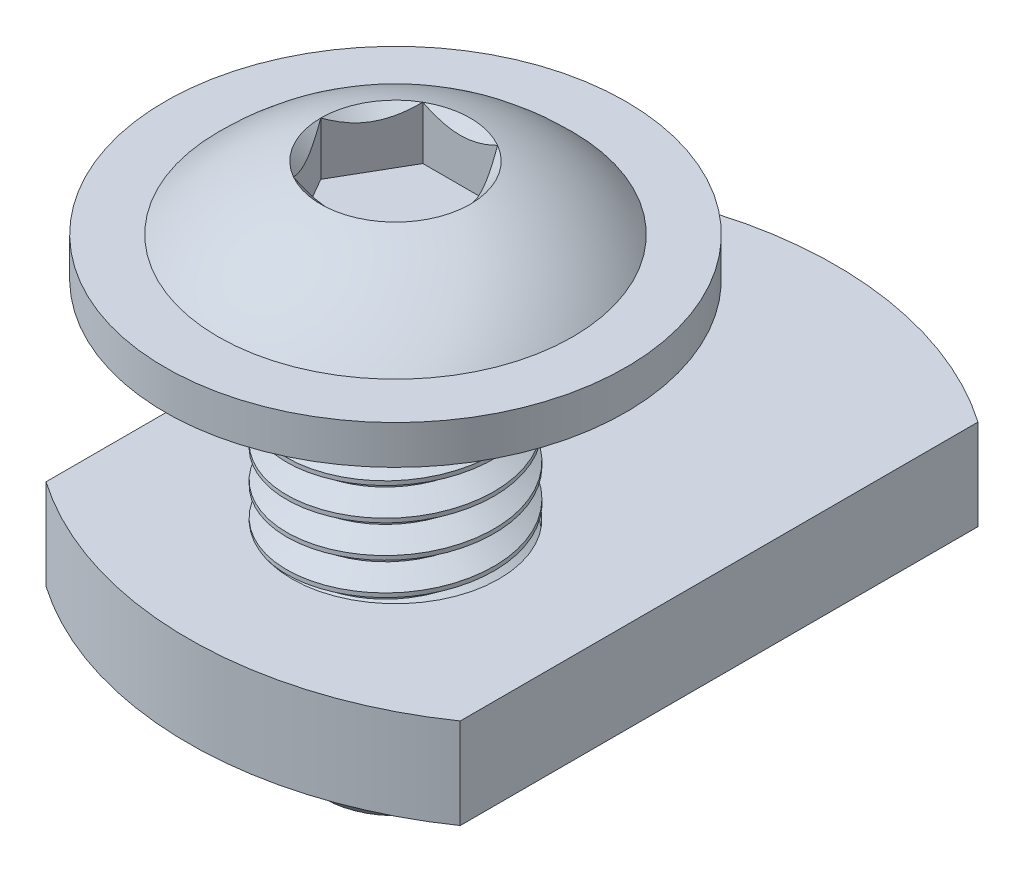
SolidWorks part; units mm, degrees
ref_plane "Front Plane" through (0, 0, 0) normal (0, 0, 1) x (1, 0, 0)
ref_plane "Top Plane" through (0, 0, 0) normal (0, 1, 0) x (1, 0, 0)
ref_plane "Right Plane" through (0, 0, 0) normal (1, 0, 0) x (0, 0, -1)
sketch "Sketch1" plane through (0, 0, 0) normal (0, 0, 1) x (1, 0, 0)
  line L0 (0, 0) -> (0, 20.4) construction
  line L1 (0, 0) -> (-4, 0)
  line L2 (-4, 0) -> (-4, 16)
  line L3 (-4, 16) -> (-6.85, 16)
  line L4 (-6.85, 16) -> (-6.85, 17.5)
  line L6 (0, 0) -> (0, 20.4)
  arc A0 (-6.85, 17.5) -> (0, 20.4) centre (0, 10.8599) cw
  dimension "screw od" = 8
  dimension "head od" = 13.7
  dimension "D4" = 1.5
  dimension "head height" = 4.4
  dimension "screw length" = 16
sketch "Sketch2" plane through (0, 0, 0) normal (0, 0, 1) x (1, 0, 0)
  line L0 (0, 0) -> (0, 20.4) construction
  line L1 (-4, 16) -> (-6.85, 16) construction
  line L2 (0, 0) -> (-4, 0) construction
  line L3 (-4, 0) -> (-4, 16) construction
  line L4 (0, 0) -> (0, 16)
  line L5 (0, 16) -> (-4, 16)
  line L6 (0, 0) -> (-4, 0)
  line L7 (-4, 0) -> (-4, 16)
revolve "Revolve2" add sketch "Sketch2" angle 360 about L0
sketch "Sketch3" plane through (0, 16, 0) normal (0, 1, 0) x (1, 0, 0)
  circle A1 centre (0, 0) radius 4
  circle A2 centre (0, 0) radius 4
  dimension "D1" = 0
curve "Helix/Spiral1" pitch 1.25 height 16.1875 turns 12.95 parameters "pitch"=1.25
chamfer "Chamfer1" distance 1.25 angle 45 1 edges at (0, 0, -4)
sketch "Sketch4" plane through (0, 0, 0) normal (0, 0, 1) x (1, 0, 0)
  line L0 (4, 17.0938) -> (4, 16)
  line L1 (4, 16) -> (3.1881, 16.4688)
  line L2 (3.1881, 16.4688) -> (3.1881, 16.625)
  line L3 (3.1881, 16.625) -> (4, 17.0938)
  line L4 (3.1881, 16.5469) -> (4, 16.5469) construction
  line L5 (3.5941, 16.2344) -> (3.5941, 16.8594) construction
  line L7 (4, 16) -> (-4, 16) construction
  dimension "D1" = 60
  dimension "D2" = 0.1562
  dimension "D3" = 0.625
sweep "Cut-Sweep1" cut profiles "Sketch4" path "Helix/Spiral1"
sketch "Sketch5" plane through (0, 0, 0) normal (0, 0, 1) x (1, 0, 0)
  line L0 (0, 0) -> (0, 20.4) construction
  line L1 (-4, 16) -> (-6.85, 16) construction
  line L3 (-6.85, 16) -> (-6.85, 17.5) construction
  line L4 (0, 16) -> (0, 20.4)
  line L5 (0, 16) -> (-6.85, 16)
  line L7 (-6.85, 16) -> (-6.85, 17.5)
  arc A0 (0, 20.4) -> (-6.85, 17.5) centre (0, 10.8599) ccw construction
  arc A1 (0, 20.4) -> (-6.85, 17.5) centre (0, 10.8599) ccw
revolve "Revolve3" add sketch "Sketch5" angle 360 about L0
sketch "Sketch20" plane through (0, 16, 0) normal (0, -1, 0) x (1, 0, 0)
  circle A0 centre (0, 0) radius 8.9
  dimension "D1" = 17.8
extrude "Boss-Extrude1" add sketch "Sketch20" against normal blind 1.5
ref_plane "Plane1" through (0, 20.4, 0) normal (0, 1, 0) x (-1, 0, 0)
sketch "Sketch6" plane through (0, 20.4, 0) normal (0, 1, 0) x (-1, 0, 0)
  line L1 (1.4434, 2.5) -> (-1.4434, 2.5)
  line L2 (-1.4434, 2.5) -> (-2.8868, 0)
  line L3 (-2.8868, 0) -> (-1.4434, -2.5)
  line L4 (-1.4434, -2.5) -> (1.4434, -2.5)
  line L5 (1.4434, -2.5) -> (2.8868, 0)
  line L6 (2.8868, 0) -> (1.4434, 2.5)
  circle A0 centre (0, 0) radius 2.5 construction
  dimension "hex" = 5
extrude "Cut-Extrude1" cut sketch "Sketch6" against normal blind 2.5
ref_plane "Plane2" through (0, 19.9528, 0) normal (0, 1, 0) x (-1, 0, 0)
sketch "Sketch7" plane through (0, 19.9528, 0) normal (0, 1, 0) x (-1, 0, 0)
  circle A0 centre (0, 0) radius 2.8868
extrude "Cut-Extrude2" cut sketch "Sketch7" against normal up to surface (2.0528 mm away) draft 45 and the other way through all
ref_plane "Plane3" through (0, 5.475, 0) normal (0, -1, 0) x (1, 0, 0)
sketch "Sketch8" [suppressed] plane through (0, 2.475, 0) normal (0, -1, 0) x (1, 0, 0)
  line L0 (-4, -2.5) -> (4, -2.5) construction
  line L1 (0, -2.5) -> (0, 0) construction
  line L2 (-4, 3.5) -> (-4, -8.5)
  line L4 (4, 3.5) -> (4, -8.5)
  circle A0 centre (0, 0) radius 2.5
  arc A1 (-4, 3.5) -> (4, 3.5) centre (0, -1.0833) cw
  arc A2 (-4, -8.5) -> (4, -8.5) centre (0, -3.9167) ccw
  dimension "D1" = 26.4706
  dimension "D4" = 3.9167
  dimension "D3" = 33.0883
  dimension "D2" = 12.7
extrude "Extrude1" [suppressed] add sketch "Sketch8" along normal mid plane 3 separate body
sketch "Sketch9" [suppressed] plane through (0, 0.975, 0) normal (0, -1, 0) x (1, 0, 0)
  line L2 (4, -8.5) -> (4, 3.5)
  line L3 (-4, 3.5) -> (-4, -8.5)
  line L4 (4, -8.5) -> (4, 3.5)
  line L5 (-4, 3.5) -> (-4, -8.5)
  circle A0 centre (0, 0) radius 3
  arc A2 (-4, -8.5) -> (4, -8.5) centre (0, -3.9167) ccw
  arc A3 (4, 3.5) -> (-4, 3.5) centre (0, -1.0833) ccw
  arc A4 (-4, -8.5) -> (4, -8.5) centre (0, -3.9167) ccw
  arc A5 (4, 3.5) -> (-4, 3.5) centre (0, -1.0833) ccw
  dimension "D2" = 6
  dimension "D1" = 0
extrude "Cut-Extrude3" [suppressed] cut sketch "Sketch9" against normal offset from surface (1 mm away) 2
sketch "Sketch10" plane through (0, 5.475, 0) normal (0, -1, 0) x (1, 0, 0)
  line L0 (-8, -14.5) -> (-8, 5.5)
  line L1 (8, 5.5) -> (8, -14.5)
  line L2 (-18.9844, 8) -> (0, 8) construction
  circle A0 centre (0, 0) radius 4
  arc A1 (8, 5.5) -> (-8, 5.5) centre (0, -6.05) ccw
  arc A2 (-8, -14.5) -> (8, -14.5) centre (0, -2.95) ccw
  dimension "D2" = 8
  dimension "D3" = 16
  dimension "D4" = 2.5
  dimension "D5" = 8
  dimension "D1" = 25
extrude "Extrude2" add sketch "Sketch10" along normal mid plane 5 separate body
sketch "Sketch11" plane through (0, 2.975, 0) normal (0, -1, 0) x (1, 0, 0)
  line L2 (8, -14.5) -> (8, 5.5)
  line L3 (-8, 5.5) -> (-8, -14.5)
  line L4 (8, -14.5) -> (8, 5.5)
  line L5 (-8, 5.5) -> (-8, -14.5)
  circle A0 centre (0, 0) radius 2.75 construction
  circle A3 centre (0, 0) radius 4.5
  arc A5 (-8, -14.5) -> (8, -14.5) centre (0, -2.95) ccw
  arc A6 (8, 5.5) -> (-8, 5.5) centre (0, -6.05) ccw
  arc A7 (-8, -14.5) -> (8, -14.5) centre (0, -2.95) ccw
  arc A8 (8, 5.5) -> (-8, 5.5) centre (0, -6.05) ccw
  dimension "D1" = 9
  dimension "D2" = 0
extrude "Cut-Extrude4" cut sketch "Sketch11" against normal offset from surface (1.5 mm away) 3.5 up to face at (0, 7.975, -4.5)
sketch "Sketch12" [suppressed] plane through (0, 0, 0) normal (0, 0, 1) x (1, 0, 0)
  line L0 (-6.8072, 17.78) -> (-5.4458, 17.78) construction
  line L1 (-6.8072, 17.78) -> (-5.4458, 17.78)
  line L2 (9.2481, 20.0393) -> (-9.2481, 20.0393) construction
  line L3 (0, 0) -> (0, 53.1234) construction
  line L4 (-3.9688, 15.875) -> (-6.8072, 15.875) construction
  line L5 (-9.398, 15.875) -> (-3.9688, 15.875)
  line L6 (-9.398, 15.875) -> (-9.398, 14.605)
  line L7 (-9.398, 14.605) -> (-3.9688, 14.605)
  line L8 (-3.9688, 15.875) -> (-3.9688, 14.605)
  arc A0 (0, 20.6375) -> (-5.4458, 17.78) centre (0, 14.0195) ccw construction
  arc A1 (-2.7496, 20.0393) -> (-5.4458, 17.78) centre (0, 14.0195) ccw
  arc A2 (-6.8072, 17.78) -> (-2.7496, 20.0393) centre (0, 10.3277) cw
  dimension "D1" = 9.398
  dimension "D2" = 1.27
revolve "Revolve4" [suppressed] add sketch "Sketch12" angle 360 about L0
sketch "Sketch13" [suppressed] plane through (0, 6.35, 0) normal (0, -1, 0) x (1, 0, 0)
  line L0 (-7.9375, 4.7562) -> (-7.9375, -17.4688)
  line L1 (7.9375, 4.7562) -> (7.9375, -17.4688)
  circle A0 centre (0, 0) radius 3.9688
  arc A1 (-7.9375, 4.7562) -> (7.9375, 4.7562) centre (0, -3.5782) cw
  arc A2 (-7.9375, -17.4688) -> (7.9375, -17.4688) centre (0, -9.1345) ccw
  dimension "D2" = 28.575
  dimension "D3" = 3.9624
  dimension "D4" = 7.9375
  dimension "D1" = 15.875
  dimension "D5" = 3.175
extrude "Extrude4" [suppressed] add sketch "Sketch13" along normal mid plane 5.8928 separate body
sketch "Sketch14" [suppressed] plane through (0, 3.4036, 0) normal (0, -1, 0) x (1, 0, 0)
  line L2 (-7.9375, 4.7561) -> (-7.9375, -17.4688)
  line L3 (7.9375, -17.4688) -> (7.9375, 4.7562)
  line L4 (-7.9375, 4.7561) -> (-7.9375, -17.4688)
  line L5 (7.9375, -17.4688) -> (7.9375, 4.7562)
  arc A2 (7.9375, 4.7562) -> (-7.9375, 4.7561) centre (0, -3.5782) ccw
  arc A3 (-7.9375, -17.4688) -> (7.9375, -17.4688) centre (0, -9.1345) ccw
  arc A4 (7.9375, 4.7562) -> (-7.9375, 4.7561) centre (0, -3.5782) ccw
  arc A5 (-7.9375, -17.4688) -> (7.9375, -17.4688) centre (0, -9.1345) ccw
  circle A6 centre (0, 0) radius 5.4927
  circle A7 centre (0, 0) radius 5.4927
  dimension "D1" = 0
  dimension "D2" = 1.524
extrude "Cut-Extrude7" [suppressed] cut sketch "Sketch14" against normal offset from surface (1.8034 mm away) 4.0894
sketch "Sketch15" [suppressed] plane through (0, 0, 0) normal (0, 0, 1) x (1, 0, 0)
  line L0 (-6.6675, 19.6774) -> (-6.9, 17.3714) construction
  line L1 (-6.6675, 19.6774) -> (-6.9, 17.3714)
  line L2 (7.59, 20.3045) -> (-7.59, 20.3045) construction
  line L3 (0, 0) -> (0, 53.1234) construction
  arc A0 (0, 20.8) -> (-6.9, 17.3714) centre (0, 12.1426) ccw construction
  arc A1 (-2.8868, 20.3045) -> (-6.9, 17.3714) centre (0, 12.1426) ccw
  arc A2 (-2.8868, 20.3045) -> (-6.6675, 19.6774) centre (0, -8.8073) ccw
revolve "Revolve5" [suppressed] add sketch "Sketch15" angle 360 about L0
sketch "Sketch16" [suppressed] plane through (0, 3.175, 0) normal (0, -1, 0) x (1, 0, 0)
  line L0 (-6.3881, 8.443) -> (-6.3881, -33.843)
  line L1 (6.3881, 8.443) -> (6.3881, -33.843)
  line L2 (0, -25.4) -> (0, 0) construction
  line L3 (0, -12.7) -> (-6.3881, -12.7) construction
  line L4 (-6.3881, -27.1355) -> (-6.3881, 1.7355) construction
  circle A0 centre (0, 0) radius 3.175
  circle A1 centre (0, -25.4) radius 3.175
  arc A2 (-6.3881, 8.443) -> (6.3881, 8.443) centre (0, 1.7355) cw
  arc A3 (-6.3881, -33.843) -> (6.3881, -33.843) centre (0, -27.1355) ccw
  dimension "D1" = 25.4
  dimension "D2" = 6.35
  dimension "D4" = 47.3964
  dimension "D3" = 12.7762
  dimension "D5" = 2.5552
extrude "Extrude5" [suppressed] add sketch "Sketch16" along normal mid plane 4.0894 separate body
sketch "Sketch17" [suppressed] plane through (0, 1.1303, 0) normal (0, -1, 0) x (1, 0, 0)
  line L2 (-6.3881, 8.443) -> (-6.3881, -33.843)
  line L3 (6.3881, -33.843) -> (6.3881, 8.443)
  line L4 (-6.3881, 8.443) -> (-6.3881, -33.843)
  line L5 (6.3881, -33.843) -> (6.3881, 8.443)
  arc A2 (6.3881, 8.443) -> (-6.3881, 8.443) centre (0, 1.7355) ccw
  arc A3 (-6.3881, -33.843) -> (6.3881, -33.843) centre (0, -27.1355) ccw
  arc A4 (6.3881, 8.443) -> (-6.3881, 8.443) centre (0, 1.7355) ccw
  arc A5 (-6.3881, -33.843) -> (6.3881, -33.843) centre (0, -27.1355) ccw
  circle A6 centre (0, -25.4) radius 4.699
  circle A7 centre (0, -25.4) radius 4.699
  circle A10 centre (0, 0) radius 4.699
  circle A11 centre (0, 0) radius 4.699
  dimension "D1" = 0
  dimension "D2" = 1.524
  dimension "D3" = 1.524
pattern_linear "LPattern1" [suppressed] count 2 spacing 25.4
extrude "Cut-Extrude9" [suppressed] cut sketch "Sketch17" against normal offset from surface (1.4224 mm away) 2.667
sketch "Sketch18" [suppressed] plane through (0, 7.9375, 0) normal (0, -1, 0) x (1, 0, 0)
  line L0 (-7.9375, 13.462) -> (-7.9375, -51.562)
  line L1 (7.9375, 13.462) -> (7.9375, -51.562)
  line L2 (0, 0) -> (0, -38.1) construction
  line L3 (0, -19.05) -> (-7.9375, -19.05) construction
  line L4 (0, -19.05) -> (7.9375, -19.05) construction
  circle A0 centre (0, 0) radius 3.9688
  circle A1 centre (0, -38.1) radius 3.9688
  arc A2 (-7.9375, 13.462) -> (7.9375, 13.462) centre (0, 5.1276) cw
  arc A3 (-7.9375, -51.562) -> (7.9375, -51.562) centre (0, -43.2276) ccw
  dimension "D1" = 38.1
  dimension "D2" = 7.9375
  dimension "D4" = 3.175
  dimension "D5" = 71.374
  dimension "D3" = 15.875
extrude "Extrude6" [suppressed] add sketch "Sketch18" along normal mid plane 5.9944 separate body
sketch "Sketch19" [suppressed] plane through (0, 4.9403, 0) normal (0, -1, 0) x (1, 0, 0)
  line L2 (-7.9375, 13.462) -> (-7.9375, -51.562)
  line L3 (7.9375, -51.562) -> (7.9375, 13.462)
  line L4 (-7.9375, 13.462) -> (-7.9375, -51.562)
  line L5 (7.9375, -51.562) -> (7.9375, 13.462)
  arc A2 (7.9375, 13.462) -> (-7.9375, 13.462) centre (0, 5.1276) ccw
  arc A3 (-7.9375, -51.562) -> (7.9375, -51.562) centre (0, -43.2276) ccw
  arc A4 (7.9375, 13.462) -> (-7.9375, 13.462) centre (0, 5.1276) ccw
  arc A5 (-7.9375, -51.562) -> (7.9375, -51.562) centre (0, -43.2276) ccw
  circle A6 centre (0, 0) radius 5.4927
  circle A7 centre (0, 0) radius 5.4927
  circle A9 centre (0, -38.1) radius 5.4928
  circle A10 centre (0, -38.1) radius 5.4928
  dimension "D1" = 0
  dimension "D2" = 1.524
  dimension "D3" = 1.524
extrude "Cut-Extrude10" [suppressed] cut sketch "Sketch19" against normal offset from surface (2.1844 mm away) 3.81
pattern_linear "LPattern2" [suppressed] count 2 spacing 38.1
equation "\"D2@Sketch4\" = \"pitch@Helix/Spiral1\"*.125"
equation "\"D3@Sketch4\" = \"pitch@Helix/Spiral1\"*.5"
equation "\"D3@Helix/Spiral1\" = \"screw length@Sketch1\"+.18750"
equation "\"D1@Chamfer1\" = \"pitch@Helix/Spiral1\""
equation "\"D1@Cut-Extrude1\" = \"hex@Sketch6\"/2"
equation "\"D5@Sketch10\" = \"screw od@Sketch1\""
equation "\"D4@Sketch10\" = \"D1@Sketch10\"*.10"
equation "\"D5@Sketch13\" = \"D1@Sketch13\"*.2"
equation "\"D5@Sketch16\" = \"D3@Sketch16\"*.2"
equation "\"D4@Sketch18\" = \"D3@Sketch18\"*.2"
equation "\"D1@Sketch8\" = \"D3@Sketch8\"*.8"
